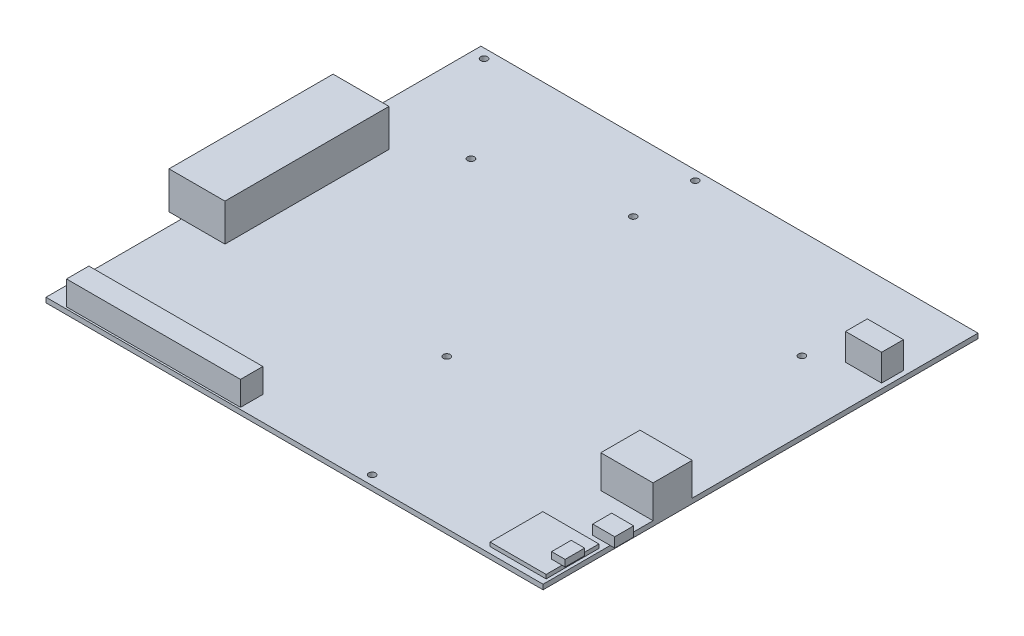
SolidWorks part; units mm, degrees
ref_plane "Front Plane" through (0, 0, 0) normal (0, 0, 1) x (1, 0, 0)
ref_plane "Top Plane" through (0, 0, 0) normal (0, 1, 0) x (1, 0, 0)
ref_plane "Right Plane" through (0, 0, 0) normal (1, 0, 0) x (0, 0, -1)
sketch "Sketch1" plane through (0, 0, 0) normal (0, 1, 0) x (1, 0, 0)
  line L1 (-101.6, -88.9) -> (101.6, -88.9)
  line L2 (-101.6, -88.9) -> (-101.6, 88.9)
  line L3 (-101.6, 88.9) -> (101.6, 88.9)
  line L4 (101.6, -88.9) -> (101.6, 88.9)
  line L5 (-101.6, -88.9) -> (101.6, 88.9) construction
  line L6 (-101.6, 88.9) -> (101.6, -88.9) construction
  point P0 (0, 0)
  dimension "D1" = 203.2
  dimension "D2" = 177.8
extrude "Boss-Extrude1" add sketch "Sketch1" along normal blind 2
sketch "Sketch3" plane through (0, 2, 0) normal (0, 1, 0) x (1, 0, 0)
  line L0 (101.6, -88.9) -> (101.6, 88.9) construction
  line L1 (101.6, -27.94) -> (80.25, -27.94)
  line L2 (101.6, -27.94) -> (101.6, -43.94)
  line L3 (101.6, -43.94) -> (80.25, -43.94)
  line L4 (80.25, -27.94) -> (80.25, -43.94)
  line L5 (-101.6, -88.9) -> (101.6, -88.9) construction
  dimension "D1" = 60.96
  dimension "D2" = 16
  dimension "D3" = 21.35
extrude "Boss-Extrude2" add sketch "Sketch3" along normal blind 13.4
sketch "Sketch2" plane through (0, 2, 0) normal (0, 1, 0) x (1, 0, 0)
  line L0 (-101.6, 88.9) -> (-101.6, -88.9) construction
  line L1 (101.6, 88.9) -> (-101.6, 88.9) construction
  line L2 (101.6, -88.9) -> (101.6, -43.94) construction
  line L3 (-101.6, -88.9) -> (101.6, -88.9) construction
  circle A0 centre (-96.52, 85.09) radius 1.397
  circle A1 centre (-10.16, 85.09) radius 1.397
  circle A2 centre (-10.16, 59.69) radius 1.397
  circle A3 centre (73.66, 44.831) radius 1.397
  circle A4 centre (-63.754, 46.99) radius 1.397
  circle A5 centre (1.27, -27.94) radius 1.397
  circle A6 centre (-96.52, -79.756) radius 1.397
  circle A7 centre (27.94, -85.09) radius 1.397
  circle A8 centre (-88.9, -30.48) radius 1.397
  circle A9 centre (-88.9, 30.48) radius 1.397
  dimension "D1" = 5.08
  dimension "D3" = 91.44
  dimension "D5" = 2.794
  dimension "D6" = 2.794
  dimension "D7" = 3.81
  dimension "D9" = 2.794
  dimension "D11" = 2.794
  dimension "D15" = 2.794
  dimension "D17" = 2.794
  dimension "D21" = 2.794
  dimension "D24" = 2.794
  dimension "D26" = 2.794
  dimension "D27" = 2.794
  dimension "D28" = 12.7
  dimension "D29" = 58.42
  dimension "D2" = 3.81
  dimension "D4" = 111.76
  dimension "D8" = 29.21
  dimension "D10" = 27.94
  dimension "D12" = 44.069
  dimension "D13" = 37.846
  dimension "D14" = 41.91
  dimension "D16" = 116.84
  dimension "D18" = 100.33
  dimension "D19" = 9.144
  dimension "D20" = 5.08
  dimension "D22" = 3.81
  dimension "D23" = 73.66
  dimension "D25" = 60.96
extrude "Cut-Extrude1" cut sketch "Sketch2" against normal through all both and the other way through all contours A0 | A1 | A2 | A4 | A5 | A3 | A9 | A8 | A7 | A6
sketch "Sketch4" plane through (0, 2, 0) normal (0, 1, 0) x (1, 0, 0)
  line L0 (-88.9, 30.48) -> (-88.9, 33.528) construction
  line L1 (-106.68, 33.528) -> (-83.82, 33.528)
  line L2 (-106.68, 33.528) -> (-106.68, -33.528)
  line L3 (-106.68, -33.528) -> (-83.82, -33.528)
  line L4 (-83.82, 33.528) -> (-83.82, -33.528)
  line L5 (-88.9, -30.48) -> (-88.9, -33.528) construction
  circle A1 centre (-88.9, 30.48) radius 1.397 construction
  dimension "D1" = 22.86
  dimension "D2" = 5.08
  dimension "D3" = 67.056
extrude "Boss-Extrude3" add sketch "Sketch4" along normal blind 15.24
sketch "Sketch5" plane through (0, 2, 0) normal (0, 1, 0) x (1, 0, 0)
  line L0 (101.6, -27.94) -> (101.6, 88.9) construction
  line L1 (84.85, 51.5) -> (99.6, 51.5)
  line L2 (84.85, 51.5) -> (84.85, 60.4)
  line L3 (84.85, 60.4) -> (99.6, 60.4)
  line L4 (99.6, 51.5) -> (99.6, 60.4)
  line L5 (101.6, 88.9) -> (-101.6, 88.9) construction
  dimension "D1" = 14.75
  dimension "D2" = 8.9
  dimension "D3" = 2
  dimension "D4" = 28.5
extrude "Boss-Extrude4" add sketch "Sketch5" along normal blind 10.922 contours L1 L4 L3 L2
sketch "Sketch7" plane through (0, 2, 0) normal (0, 1, 0) x (1, 0, 0)
  line L0 (-101.6, -88.9) -> (101.6, -88.9) construction
  line L1 (94.45, -53.7) -> (103.45, -53.7)
  line L2 (94.45, -53.7) -> (94.45, -61.45)
  line L3 (94.45, -61.45) -> (103.45, -61.45)
  line L4 (103.45, -53.7) -> (103.45, -61.45)
  line L5 (101.6, -88.9) -> (101.6, -43.94) construction
  dimension "D1" = 35.2
  dimension "D2" = 7.75
  dimension "D3" = 9
  dimension "D4" = 1.85
extrude "Boss-Extrude5" add sketch "Sketch7" along normal blind 4
sketch "Sketch8" plane through (0, 2, 0) normal (0, 1, 0) x (1, 0, 0)
  line L0 (-101.6, -88.9) -> (101.6, -88.9) construction
  line L1 (77.45, -64.83) -> (100.35, -64.83)
  line L2 (77.45, -64.83) -> (77.45, -86.4)
  line L3 (77.45, -86.4) -> (100.35, -86.4)
  line L4 (100.35, -64.83) -> (100.35, -86.4)
  line L5 (101.6, -88.9) -> (101.6, -61.45) construction
  dimension "D1" = 21.57
  dimension "D2" = 22.9
  dimension "D3" = 2.5
  dimension "D4" = 1.25
extrude "Boss-Extrude6" add sketch "Sketch8" along normal blind 1.6
sketch "Sketch9" plane through (0, 3.6, 0) normal (0, 1, 0) x (1, 0, 0)
  line L0 (-101.6, -88.9) -> (101.6, -88.9) construction
  line L1 (96.1, -71.9) -> (101.6, -71.9)
  line L2 (96.1, -71.9) -> (96.1, -79.9)
  line L3 (96.1, -79.9) -> (101.6, -79.9)
  line L4 (101.6, -71.9) -> (101.6, -79.9)
  line L5 (101.6, -88.9) -> (101.6, -61.45) construction
  dimension "D1" = 8
  dimension "D2" = 5.5
  dimension "D3" = 17
extrude "Boss-Extrude7" add sketch "Sketch9" along normal blind 2.7
sketch "Sketch10" plane through (0, 2, 0) normal (0, 1, 0) x (1, 0, 0)
  line L0 (-101.6, -33.528) -> (-101.6, -88.9) construction
  line L1 (-93.98, -88.138) -> (-22.86, -88.138)
  line L2 (-93.98, -88.138) -> (-93.98, -78.994)
  line L3 (-93.98, -78.994) -> (-22.86, -78.994)
  line L4 (-22.86, -88.138) -> (-22.86, -78.994)
  line L5 (-101.6, -88.9) -> (101.6, -88.9) construction
  dimension "D1" = 71.12
  dimension "D2" = 9.144
  dimension "D3" = 7.62
  dimension "D4" = 0.762
extrude "Boss-Extrude8" add sketch "Sketch10" along normal blind 9.906
